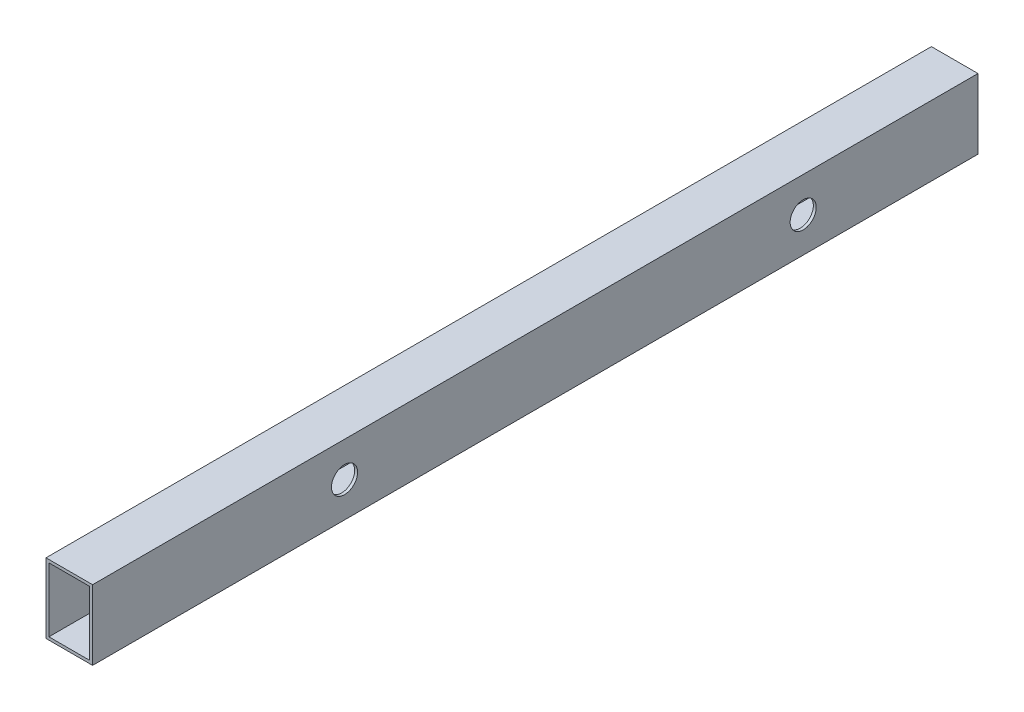
SolidWorks part; units mm, degrees
ref_plane "Front Plane" through (0, 0, 0) normal (0, 0, 1) x (1, 0, 0)
ref_plane "Top Plane" through (0, 0, 0) normal (0, 1, 0) x (1, 0, 0)
ref_plane "Right Plane" through (0, 0, 0) normal (1, 0, 0) x (0, 0, -1)
sketch "Sketch1" plane through (0, 0, 0) normal (0, 0, 1) x (1, 0, 0)
  line L0 (0, 38.1) -> (0, 34.925) construction
  line L1 (-25.4, 38.1) -> (25.4, 38.1)
  line L2 (-25.4, 38.1) -> (-25.4, -38.1)
  line L3 (-25.4, -38.1) -> (25.4, -38.1)
  line L4 (25.4, 38.1) -> (25.4, -38.1)
  line L5 (-25.4, 38.1) -> (25.4, -38.1) construction
  line L6 (-25.4, -38.1) -> (25.4, 38.1) construction
  line L7 (-22.225, 34.925) -> (22.225, 34.925)
  line L8 (-22.225, 34.925) -> (-22.225, -34.925)
  line L9 (-22.225, -34.925) -> (22.225, -34.925)
  line L10 (22.225, 34.925) -> (22.225, -34.925)
  line L11 (22.225, 0) -> (25.4, 0) construction
  line L12 (-22.225, 0) -> (-25.4, 0) construction
  line L13 (0, -34.925) -> (0, -38.1) construction
  point P0 (0, 0)
  dimension "D1" = 76.2
  dimension "D2" = 50.8
  dimension "D3" = 3.175
extrude "Boss-Extrude1" add sketch "Sketch1" along normal blind 965.2
sketch "Sketch2" plane through (0, 38.1, 0) normal (0, 1, 0) x (1, 0, 0)
  line L0 (-26.9875, -190.549) -> (26.9875, -190.549) construction
  line L1 (-25.4, 0) -> (25.4, 0)
  line L2 (-25.4, 0) -> (-25.4, -965.2)
  line L3 (-25.4, -965.2) -> (25.4, -965.2)
  line L4 (25.4, 0) -> (25.4, -965.2)
  line L5 (-26.4963, -703.2466) -> (26.4963, -703.2466) construction
  line L6 (0, -703.2466) -> (0, -190.549) construction
  line L7 (0, 0) -> (0, -190.549) construction
  line L8 (-74.6125, -402.6047) -> (-73.6301, -528.6965) construction
  line L9 (-74.1213, -465.6506) -> (-23.8125, -465.6506) construction
  line L10 (-23.8125, -465.6506) -> (26.9875, -465.6506) construction
  dimension "D1" = 190.549
  dimension "D2" = 512.6976
  dimension "D3" = 126.0917
  dimension "D4" = 50.3088
  dimension "D5" = 50.8
  dimension "D6" = 53.975
  dimension "D7" = 52.9926
  dimension "D8" = 275.1016
ref_plane "Plane1" through (25.4, 0, 0) normal (1, 0, 0) x (0, 0, -1)
sketch "Sketch4" plane through (25.4, 0, 0) normal (1, 0, 0) x (0, 0, -1)
  line L0 (-690.548, 38.1) -> (-690.548, 0) construction
  line L1 (-703.2466, 38.1) -> (-190.549, 38.1) construction
  line L2 (-190.549, 38.1) -> (-190.549, 0) construction
  line L3 (0, 38.1) -> (-190.549, 38.1) construction
  line L4 (-190.549, 0) -> (0, 0) construction
  line L5 (0, -38.1) -> (0, 38.1) construction
  line L6 (-190.549, 0) -> (-690.548, 0) construction
  circle A0 centre (-690.548, 0) radius 14.224
  circle A1 centre (-190.549, 0) radius 14.224
  dimension "D1" = 28.448
  dimension "D2" = 499.999
  dimension "D3" = 190.549
extrude "Cut-Extrude1" cut sketch "Sketch4" against normal up to surface (50.8 mm away) contours A1 | A0 up to face at (-25.4, 0, 482.6)
sketch "Sketch5" plane through (0, -38.1, 0) normal (0, -1, 0) x (1, 0, 0)
  line L0 (0, 0) -> (0, 283.21) construction
  line L1 (0, 283.21) -> (-25.4, 283.21) construction
  line L2 (-25.4, 965.2) -> (-25.4, 0) construction
  line L3 (-19.05, 283.21) -> (-19.05, 276.86) construction
  line L4 (-19.05, 283.21) -> (-19.05, 289.56) construction
  circle A0 centre (-19.05, 276.86) radius 2.6445
  circle A1 centre (-19.05, 289.56) radius 3.032
  dimension "D1" = 283.21
  dimension "D2" = 6.35
  dimension "D3" = 6.35
  dimension "D4" = 6.35
extrude "Cut-Extrude2" cut sketch "Sketch5" against normal up to surface (3.175 mm away) up to face at (0, -34.925, 482.6)
